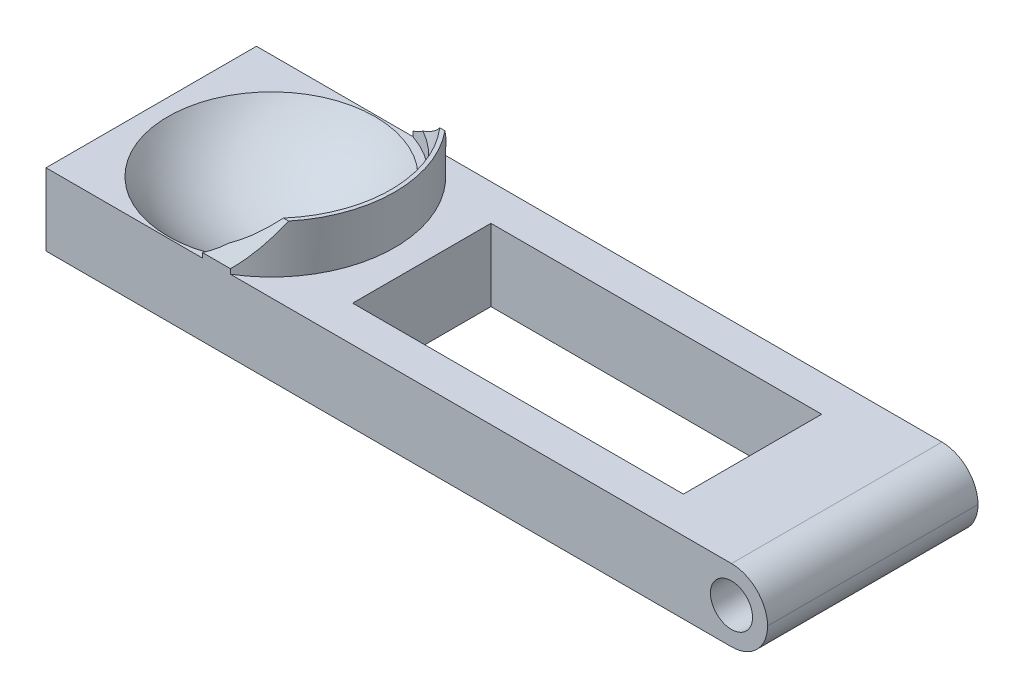
SolidWorks part; units mm, degrees
ref_plane "Front" through (0, 0, 0) normal (0, 0, 1) x (1, 0, 0)
ref_plane "Top" through (0, 0, 0) normal (0, 1, 0) x (1, 0, 0)
ref_plane "Right" through (0, 0, 0) normal (1, 0, 0) x (0, 0, -1)
sketch "Sketch1" plane through (0, 0, 0) normal (0, 1, 0) x (1, 0, 0)
  line L1 (-60, 17.5) -> (60, 17.5)
  line L2 (-60, 17.5) -> (-60, -17.5)
  line L3 (-60, -17.5) -> (60, -17.5)
  line L4 (60, 17.5) -> (60, -17.5)
  line L5 (-60, 17.5) -> (60, -17.5) construction
  line L6 (-60, -17.5) -> (60, 17.5) construction
  point P0 (0, 0)
  dimension "D1" = 35
  dimension "D2" = 120
extrude "Boss-Extrude1" add sketch "Sketch1" along normal mid plane 12
fillet "Fillet1" radius 6 2 edges at (60, 6, 0) (60, -6, 0)
sketch "Sketch2" plane through (0, 0, 0) normal (0, 0, 1) x (1, 0, 0)
  line L0 (-60, 6) -> (-60, -6) construction
  line L1 (-60, 6) -> (54, 6) construction
  line L2 (-61, 18) -> (-19, 18)
  arc A0 (-19, 18) -> (-61, 18) centre (-40, 18) ccw
  dimension "D1" = 42
  dimension "D2" = 20
  dimension "D3" = 12
revolve "Cut-Revolve1" cut sketch "Sketch2" angle 360 about L2
hole_wizard "Ø6.0mm Dowel Hole1" positions "Sketch3" profile "Sketch4" hole size "Ø6.0" standard "ANSI Metric" end condition through all
sketch "Sketch3" plane through (0, 0, 17.5) normal (0, 0, 1) x (1, 0, 0)
  point P0 (54, 0)
sketch "Sketch4" plane through (54, 0, 17.5) normal (1, 0, 0) x (0, -1, 0)
  line L0 (0, 0) -> (0, 35)
  line L1 (0, 35) -> (3.5, 35)
  line L2 (3.5, 35) -> (3.5, 0)
  line L5 (3.5, 0) -> (0, 0)
  line L11 (0, -6.35) -> (0, 107.95) construction
  dimension "Thru Hole Dia." = 7
  dimension "Thru Hole Depth" = 35
sketch "Sketch5" plane through (0, -6, 0) normal (0, -1, 0) x (1, 0, 0)
  line L0 (-60, 17.5) -> (54, 17.5) construction
  line L1 (-60, -17.5) -> (-60, 17.5) construction
  line L2 (50, 0) -> (-50, 0) construction
  circle A0 centre (-45.5, 10) radius 5.25
  circle A1 centre (-45.5, -10) radius 5.25
  dimension "D1" = 10.5
  dimension "D2" = 7.5
  dimension "D3" = 14.5
extrude "Cut-Extrude1" cut sketch "Sketch5" against normal blind 2
sketch "Sketch6" plane through (0, 6, 0) normal (0, 1, 0) x (1, 0, 0)
  line L0 (-60, 17.5) -> (-60, -17.5) construction
  line L1 (-15, 11.5) -> (40, 11.5)
  line L2 (-15, 11.5) -> (-15, -11.5)
  line L3 (-15, -11.5) -> (40, -11.5)
  line L4 (40, 11.5) -> (40, -11.5)
  point P6 (-15, 0)
  dimension "D1" = 45
  dimension "D2" = 55
  dimension "D3" = 23
extrude "Cut-Extrude2" cut sketch "Sketch6" against normal through all
sketch "Sketch7" [suppressed] plane through (0, 7.5, 0) normal (0, 1, 0) x (1, 0, 0)
  line L1 (40, -7.4525) -> (40, -11.4525)
  line L3 (-15, -7.4525) -> (-4.0577, 11.5)
  line L5 (-15, 11.5) -> (-15, -11.5) construction
  line L13 (40, 11.5) -> (-15, 11.5) construction
  line L14 (-4.0577, 11.5) -> (-0.3077, 11.5)
  line L15 (-0.3077, 11.5) -> (11.8166, -9.5)
  line L16 (11.8166, -9.5) -> (13.1834, -9.5)
  line L22 (13.1834, -9.5) -> (25.3077, 11.5)
  line L23 (25.3077, 11.5) -> (29.0577, 11.5)
  line L24 (29.0577, 11.5) -> (40, -7.4525)
  line L25 (40, -11.5) -> (40, 11.5) construction
  line L28 (-15, -11.5) -> (40, -11.5) construction
  line L30 (26.4624, 9.5) -> (14.3381, -11.5)
  line L31 (14.3381, -11.5) -> (10.6619, -11.5)
  line L32 (10.6619, -11.5) -> (-1.4624, 9.5)
  line L35 (-15, -11.4525) -> (-15, -7.4525)
  line L36 (26.4624, 9.5) -> (27.903, 9.5)
  line L37 (27.903, 9.5) -> (40, -11.4525)
  line L38 (-1.4624, 9.5) -> (-2.903, 9.5)
  line L39 (-2.903, 9.5) -> (-15, -11.4525)
  point P6 (-2.1827, 9.5)
  point P16 (40, -10.3689)
  point P17 (13.5004, -9.5)
  point P24 (0, 0)
  point P26 (40, -10.3689)
  point P27 (40, -10.3689)
  point P30 (-2.1827, 11.5)
  point P31 (27.1827, 11.5)
  point P32 (27.1827, 9.5)
  point P33 (-15, -10.3689)
  point P34 (12.5, -11.5)
  point P35 (12.5, -11.5)
  point P36 (-1.4624, 9.5)
  point P37 (0, 0)
  dimension "D1" = 60
  dimension "D2" = 60
  dimension "D3" = 60
  dimension "D4" = 60
  dimension "D5" = 2
  dimension "D6" = 2
  dimension "D7" = 2
  dimension "D8" = 2
  dimension "D9" = 2
  dimension "D10" = 3.75
  dimension "D11" = 3.75
sketch "Sketch8" plane through (0, 6, 0) normal (0, 1, 0) x (1, 0, 0)
  line L0 (-26.8376, 13) -> (-24.1491, 13)
  line L1 (-26.8376, -13) -> (-24.1491, -13)
  arc A0 (-24.1491, -13) -> (-24.1491, 13) centre (-40, 0) ccw
  arc A1 (-26.8376, -13) -> (-26.8376, 13) centre (-40, 0) ccw
  circle A2 centre (-40, 0) radius 17.2337 construction
  point P1 (0, 0)
  dimension "D1" = 20.5
  dimension "D2" = 18.5
  dimension "D3" = 13
  dimension "D4" = 13
extrude "Boss-Extrude4" add sketch "Sketch8" along normal blind 8
chamfer "Chamfer1" distance 5 angle 15 1 edges at (-21.5, 14, 0) first distance on face at (-24.1688, 10, 0)
chamfer "Chamfer2" distance 5 angle 58 2 edges at (-25.4933, 6, 13) (-25.4933, 6, -13) first distance on face at (12.5, 6, 0)
